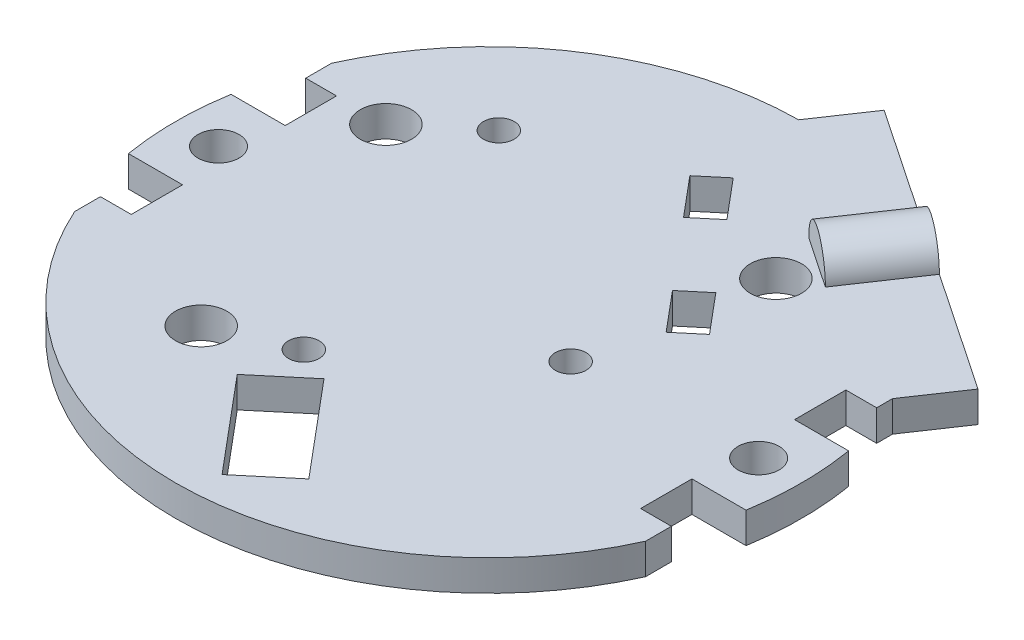
SolidWorks part; units mm, degrees
ref_plane "Alzado" through (0, 0, 0) normal (0, 0, 1) x (1, 0, 0)
ref_plane "Planta" through (0, 0, 0) normal (0, 1, 0) x (1, 0, 0)
ref_plane "Vista lateral" through (0, 0, 0) normal (1, 0, 0) x (0, 0, -1)
sketch "Croquis1" plane through (0, 0, 0) normal (0, 1, 0) x (1, 0, 0)
  circle A0 centre (0, 0) radius 30.5
extrude "Saliente-Extruir1" add sketch "Croquis1" along normal blind 3
sketch "Croquis5" plane through (0, 3, 0) normal (0, 1, 0) x (1, 0, 0)
  line L0 (0, 0) -> (0, 10)
  line L1 (28.8141, -5) -> (30.0874, -5)
  line L2 (28.8141, 5) -> (30.0874, 5)
  line L3 (-24.8141, 10) -> (-28.8141, 10)
  line L4 (24.8141, -5) -> (24.8141, -10)
  line L5 (-24.8141, -10) -> (-28.8141, -10)
  line L6 (24.8141, -5) -> (28.8141, -5)
  line L7 (24.8141, 5) -> (24.8141, 10)
  line L8 (-24.8141, 5) -> (-28.8141, 5)
  line L9 (-24.8141, 5) -> (-24.8141, 10)
  line L10 (-24.8141, -5) -> (-28.8141, -5)
  line L11 (-24.8141, -5) -> (-24.8141, -10)
  line L12 (24.8141, 5) -> (28.8141, 5)
  line L13 (24.8141, -10) -> (28.8141, -10)
  line L14 (24.8141, 10) -> (28.8141, 10)
  line L15 (-28.8141, 5) -> (-30.0874, 5)
  line L16 (-28.8141, -5) -> (-30.0874, -5)
  circle A1 centre (0, 0) radius 30.5 construction
  arc A2 (-28.8141, 10) -> (-30.0874, 5) centre (0, 0) ccw
  arc A3 (28.8141, 10) -> (28.8141, -10) centre (0, 0) cw
  arc A4 (-30.0874, -5) -> (-28.8141, -10) centre (0, 0) ccw
  arc A5 (30.0874, -5) -> (28.8141, -10) centre (0, 0) cw
  arc A6 (28.8141, 10) -> (30.0874, 5) centre (0, 0) cw
  circle M2 centre (0, 0) radius 30.5
extrude "Cortar-Extruir3" cut sketch "Croquis5" against normal blind 4 contours L11 L10 L8 L9 L3 L5 M2 | L15 L8 L9 L3 M2 | L14 L7 L12 L2 M2 | L4 L13 L1 L6 M2 region at (27.1844, 3, 7.3876) region at (27.1844, 3, -7.3876) region at (-27.1844, 3, 7.3876) region at (-27.1844, 3, -7.3876)
sketch "Croquis7" plane through (0, 3, 0) normal (0, 1, 0) x (1, 0, 0)
  line L0 (-8.1011, 29.1011) -> (9.5756, 8.0348)
  line L1 (9.5756, 8.0348) -> (27.2522, -13.0314)
  line L2 (-8.1011, 29.1011) -> (-27.2522, 13.0314)
  line L3 (27.2522, -13.0314) -> (8.1011, -29.1011)
  line L4 (8.1011, -29.1011) -> (-27.2522, 13.0314)
  line L5 (1.4284, 22.4114) -> (-0.8697, 20.4831)
  line L6 (1.4284, 22.4114) -> (4.6423, 18.5812)
  line L7 (4.6423, 18.5812) -> (2.3442, 16.6528)
  line L8 (2.3442, 16.6528) -> (-0.8697, 20.4831)
  line L9 (7.9686, 9.95) -> (11.1825, 6.1197)
  line L10 (8.1011, -29.1011) -> (5.53, -26.0369)
  line L11 (10.2667, 11.8783) -> (13.4807, 8.0481)
  line L12 (13.4807, 8.0481) -> (11.1825, 6.1197)
  line L13 (10.2667, 11.8783) -> (7.9686, 9.95)
  line L14 (5.53, -26.0369) -> (10.8923, -21.5374)
  line L15 (10.8923, -21.5374) -> (-19.3188, 14.4667)
  line L17 (-24.6811, 9.9672) -> (-19.3188, 14.4667)
  point P7 (-9.5756, -8.0348)
extrude "Cortar-Extruir5" cut sketch "Croquis7" against normal blind 4 contours L7 L6 L5 L0 | L11 L13 L0 L1 L12 region at (1.8863, 3, -19.5321) region at (10.7246, 3, -8.999)
sketch "Croquis8" plane through (0, 3, 0) normal (0, 1, 0) x (1, 0, 0)
  line L0 (-11.3137, 11.3137) -> (0, 0)
  line L2 (0, 0) -> (12, 0)
  line L3 (0, 0) -> (-11.3137, 11.3137)
  line L4 (12, 0) -> (12, 16)
  line L5 (0, 0) -> (-12, 0)
  line L6 (-12, 0) -> (-12, -16)
  line L10 (1.5586, -27.5246) -> (6.1549, -23.6679)
  line L11 (6.1549, -23.6679) -> (-1.5586, -14.4754)
  line L13 (-6.1549, -18.3321) -> (-1.5586, -14.4754)
  line L14 (1.5586, -27.5246) -> (-6.1549, -18.3321)
  circle A0 centre (0, 0) radius 30
  circle A1 centre (9, -1) radius 1.5
  circle A2 centre (-5, -13) radius 1.5
  circle A3 centre (-12, -16) radius 2.5
  circle A4 centre (-14, 15) radius 1.5
  circle A5 centre (12, 16) radius 2.5
  point P20 (-3.8567, -16.4037)
extrude "Cortar-Extruir6" cut sketch "Croquis8" against normal blind 10 contours L13 L10 L11 | A3 | L6 A3 | A3 L6 | A5 | L4 A5 | A5 L4 | L14 L10 L11 | L14 L11 | L13 L11 | A4 | L2 A1 | L2 A1 | A2 region at (10.2822, 3, -17.7178) region at (9, 3, -0.2032) region at (9, 3, 1.148) region at (-10.2822, 3, 14.2822) region at (0, 3, 21) region at (-5, 3, 13) region at (-14, 3, -15)
sketch "Croquis10" plane through (0, 3, 0) normal (0, 1, 0) x (1, 0, 0)
  line L0 (-24.8141, 10) -> (-27.8141, 10)
  line L2 (-24.8141, 10) -> (-28.8141, 10) construction
  line L4 (-27.8141, 10) -> (-27.8141, 12.5151)
  line L6 (-27.8141, 10) -> (-28.8141, 10)
  line L14 (-27.8141, -10) -> (-28.8141, -10)
  line L15 (-27.8141, -10) -> (-27.8141, -12.5151)
  line L16 (27.8141, -10) -> (27.8141, -12.5151)
  line L17 (27.8141, -10) -> (28.8141, -10)
  line L21 (27.8141, 10) -> (28.8141, 10)
  line L22 (27.8141, 10) -> (27.8141, 12.5151)
  line L23 (24.8141, 10) -> (27.8141, 10)
  circle A0 centre (-26.3141, 0) radius 2
  circle A1 centre (26.3141, 0) radius 2
  arc A2 (28.8141, 10) -> (-28.8141, 10) centre (0, 0) ccw construction
  arc A5 (-27.8141, 12.5151) -> (-28.8141, 10) centre (0, 0) ccw
  arc A7 (-27.8141, -12.5151) -> (-28.8141, -10) centre (0, 0) cw
  arc A8 (27.8141, -12.5151) -> (28.8141, -10) centre (0, 0) ccw
  arc A10 (27.8141, 12.5151) -> (28.8141, 10) centre (0, 0) cw
  line M13 (24.8141, 10) -> (28.8141, 10)
  arc M14 (28.8141, 10) -> (-28.8141, 10) centre (0, 0) ccw
  line M15 (-28.8141, 10) -> (-24.8141, 10)
  line M21 (-24.8141, -10) -> (-28.8141, -10)
  arc M22 (-28.8141, -10) -> (28.8141, -10) centre (0, 0) ccw
  line M23 (28.8141, -10) -> (24.8141, -10)
extrude "Cortar-Extruir8" cut sketch "Croquis10" against normal blind 3 contours L15 M21 M22 | L4 M15 M14 | L16 M23 M22 | L22 M13 M14 | A0 | A1 | L22 A10 L21 region at (-28.1547, 3, -10.8559) region at (28.1547, 3, -10.8559) region at (-28.1547, 3, 10.8559) region at (28.1547, 3, 10.8559) region at (-26.3141, 3, 0) region at (26.3141, 3, 0)
sketch "Croquis11" plane through (0, 3, 0) normal (0, 1, 0) x (1, 0, 0)
  line L0 (0, 0) -> (-20, 0)
  line L1 (-20, 0) -> (-20, 10)
  line L2 (0, 0) -> (0, 4.5949)
  line L3 (29.8013, 10.2046) -> (-1.7022, 31.454)
  circle A0 centre (-20, 10) radius 2.5
  circle A5 centre (0, 0) radius 31.5
  line M20 (27.8141, 10) -> (27.8141, 12.5151)
  arc M21 (27.8141, 12.5151) -> (-27.8141, 12.5151) centre (0, 0) ccw
extrude "Cortar-Extruir9" cut sketch "Croquis11" against normal blind 3 contours L3 M20 M21 | A0 region at (15.2326, 3, -22.6507) region at (-18.2822, 3, -8.2822)
sketch "Croquis13" plane through (14.0495, 0, -20.8293) normal (0.5592, 0, -0.829) x (-0.829, 0, -0.5592)
  line L1 (-16.603, 0) -> (17.2916, 0)
  line L2 (-16.603, 0) -> (-16.603, 3)
  line L3 (-16.603, 3) -> (17.2916, 3)
  line L4 (17.2916, 0) -> (17.2916, 3)
extrude "Saliente-Extruir2" add sketch "Croquis13" along normal blind 6
sketch "Croquis14" plane through (17.4047, 0, -25.8035) normal (0.5592, 0, -0.829) x (-0.829, 0, -0.5592)
  line L1 (17.2916, 3) -> (-16.603, 3) construction
  circle A0 centre (0.3443, 3) radius 3
extrude "Saliente-Extruir3" add sketch "Croquis14" against normal blind 8
sketch "Croquis17" plane through (17.4047, 0, -25.8035) normal (0.5592, 0, -0.829) x (-0.829, 0, -0.5592)
  circle A0 centre (0.3443, 3) radius 1.5
extrude "Cortar-Extruir10" cut sketch "Croquis17" against normal blind 7
